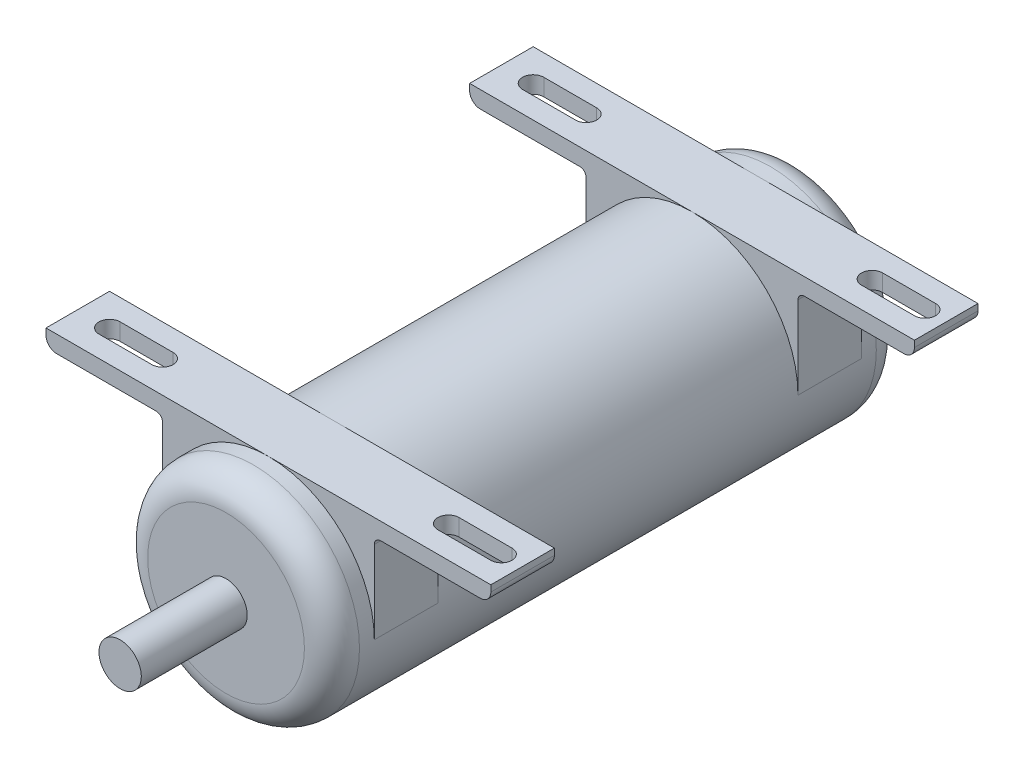
SolidWorks part; units mm, degrees
ref_plane "Front Plane" through (0, 0, 0) normal (0, 0, 1) x (1, 0, 0)
ref_plane "Top Plane" through (0, 0, 0) normal (0, 1, 0) x (1, 0, 0)
ref_plane "Right Plane" through (0, 0, 0) normal (1, 0, 0) x (0, 0, -1)
sketch "Sketch1" plane through (0, 0, 0) normal (0, 0, 1) x (1, 0, 0)
  circle A0 centre (0, 0) radius 50
  dimension "D1" = 100
extrude "Boss-Extrude1" add sketch "Sketch1" along normal blind 270
sketch "Sketch2" plane through (0, 0, 270) normal (0, 0, 1) x (1, 0, 0)
  circle A0 centre (0, 0) radius 10
  dimension "D1" = 20
extrude "Boss-Extrude2" add sketch "Sketch2" along normal blind 50
sketch "Sketch3" plane through (0, 0, 0) normal (0, 1, 0) x (1, 0, 0)
  line L0 (50, 0) -> (-50, 0) construction
  line L1 (-105, -20) -> (105, -20)
  line L2 (-105, -20) -> (-105, -50)
  line L3 (-105, -50) -> (105, -50)
  line L4 (105, -20) -> (105, -50)
  dimension "D1" = 30
  dimension "D2" = 210
  dimension "D3" = 105
  dimension "D4" = 20
extrude "Boss-Extrude3" add sketch "Sketch3" along normal blind 50
ref_plane "Plane1" through (0, 0, 135) normal (0, 0, 1) x (1, 0, 0)
mirror "Mirror1" about plane through (0, 0, 135) normal (0, 0, 1) of "Boss-Extrude3"
sketch "Sketch4" plane through (0, 0, 250) normal (0, 0, 1) x (1, 0, 0)
  line L0 (-50, 0) -> (-50, 42)
  line L1 (-50, 42) -> (-105, 42)
  line L2 (-105, 50) -> (-105, 0) construction
  line L3 (-105, 42) -> (-105, 0)
  line L4 (-105, 0) -> (-50, 0)
  dimension "D1" = 8
extrude "Cut-Extrude1" cut sketch "Sketch4" against normal blind 50
pattern_linear "LPattern2" count 2 spacing 200 along (0, 0, -1) of "Cut-Extrude1"
mirror "Mirror2" about plane through (0, 0, 0) normal (1, 0, 0) of "LPattern2"
sketch "Sketch7" plane through (0, 50, 0) normal (0, 1, 0) x (-1, 0, 0)
  line L0 (105, 35) -> (-105, 35) construction
  line L2 (105, 20) -> (105, 50) construction
  line L3 (-105, 50) -> (-105, 20) construction
  line L4 (90, 30) -> (65, 30)
  line L5 (90, 40) -> (65, 40)
  arc A0 (90, 40) -> (90, 30) centre (90, 35) cw
  arc A1 (65, 30) -> (65, 40) centre (65, 35) cw
  dimension "D1" = 10
  dimension "D2" = 5
  dimension "D3" = 15
  dimension "D4" = 25
extrude "Cut-Extrude2" cut sketch "Sketch7" against normal through all
pattern_linear "LPattern4" count 2 spacing 160 along (1, 0, 0) count 2 spacing 200 along (0, 0, 1) of "Cut-Extrude2"
fillet "Fillet1" radius 5 4 edges at (105, 42, 235) (-105, 42, 235) (105, 42, 35) (-105, 42, 35)
fillet "Fillet2" radius 3 4 edges at (50, 42, 235) (50, 42, 35) (-50, 42, 35) (-50, 42, 235)
fillet "Fillet3" radius 13 2 edges at (50, 0, 0) (50, 0, 270)
